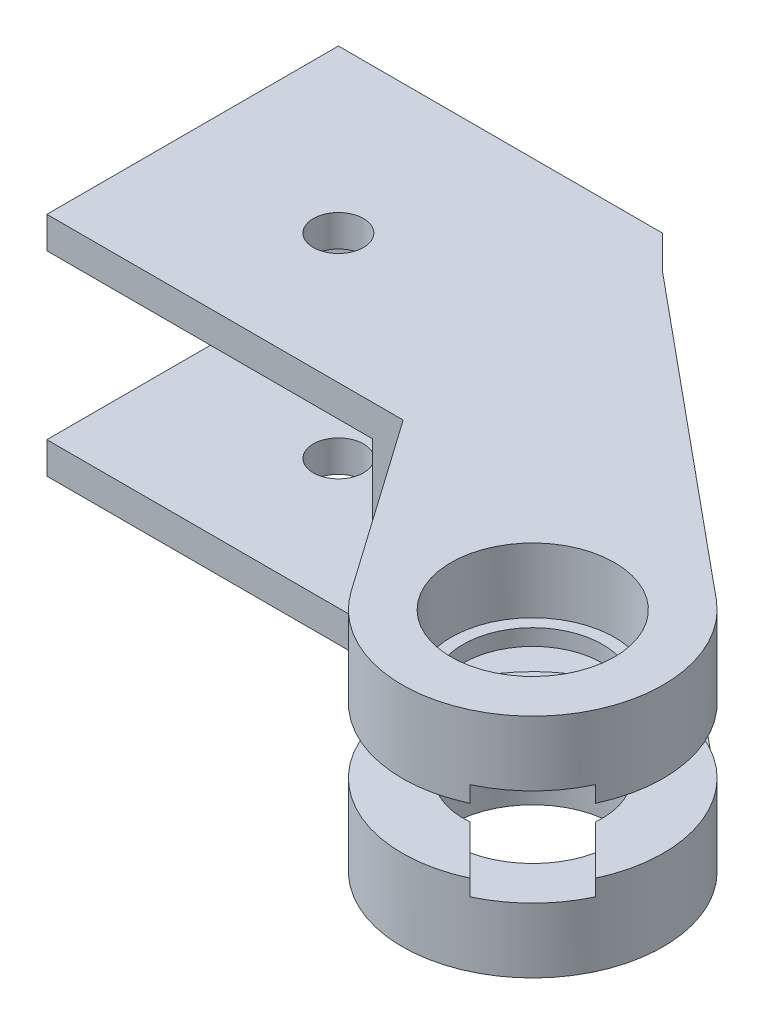
SolidWorks part; units mm, degrees
material "PET-G 50%"
ref_plane "Front Plane" through (0, 0, 0) normal (0, 0, 1) x (1, 0, 0)
ref_plane "Top Plane" through (0, 0, 0) normal (0, 1, 0) x (1, 0, 0)
ref_plane "Right Plane" through (0, 0, 0) normal (1, 0, 0) x (0, 0, -1)
sketch "Sketch1" plane through (0, 0, 0) normal (0, 1, 0) x (1, 0, 0)
  line L0 (0, 0) -> (0, 30319.3642) construction
  line L1 (-12, 8) -> (0, 8)
  line L2 (-12, 8) -> (-12, -8)
  line L3 (-12, -8) -> (0, -8)
  line L4 (0, 8) -> (0, -8)
  line L5 (0, 0) -> (30319.3642, 0) construction
  point P11 (0, -8)
  dimension "D1" = 12
  dimension "D2" = 16
extrude "Boss-Extrude1" add sketch "Sketch1" along normal mid plane 14
ref_plane "Plane1" through (0, 0, 0) normal (0, -1, 0) x (-1, 0, 0)
sketch "Sketch4" plane through (-12, 0, 0) normal (-1, 0, 0) x (0, 0, 1)
  line L0 (-8, 7) -> (-8, -7) construction
  line L1 (-8, -5.05) -> (8, -5.05)
  line L2 (-8, -5.05) -> (-8, 5.05)
  line L3 (-8, 5.05) -> (8, 5.05)
  line L4 (8, -5.05) -> (8, 5.05)
  line L5 (8, 7) -> (8, -7) construction
  line L6 (0, 0) -> (50000, 0) construction
  dimension "D1" = 10.1
extrude "Cut-Extrude1" cut sketch "Sketch4" against normal blind 10.1
sketch "Sketch5" plane through (0, -7, 0) normal (0, -1, 0) x (1, 0, 0)
  line L0 (0, 0) -> (14.1421, 14.1421) construction
  line L1 (0, 8) -> (7.552, 18.7652)
  line L2 (0, 8) -> (0, -8)
  line L3 (0, -8) -> (19.2725, 7.9387)
  line L4 (0, 0) -> (50000, 0) construction
  circle A0 centre (14.1421, 14.1421) radius 5.05
  circle A1 centre (14.1421, 14.1421) radius 8.05 construction
  arc A2 (19.2725, 7.9387) -> (7.552, 18.7652) centre (14.1421, 14.1421) ccw
  dimension "D1" = 10.1
  dimension "D2" = 3
  dimension "D3" = 20
  dimension "D4" = 45
extrude "Boss-Extrude2" add sketch "Sketch5" against normal blind 4
mirror "Mirror1" about plane through (0, 0, 0) normal (0, -1, 0) of "Boss-Extrude2"
sketch "Sketch6" plane through (0, -3, 0) normal (0, 1, 0) x (1, 0, 0)
  line L0 (14.5351, -18.4241) -> (17.5474, -21.4364)
  line L2 (0, 0) -> (19.8343, -19.8343) construction
  line L3 (21.4364, -17.5474) -> (18.4241, -14.5351)
  circle A1 centre (14.1421, -14.1421) radius 8.05 construction
  arc A2 (14.5351, -18.4241) -> (18.4241, -14.5351) centre (14.1421, -14.1421) cw
  arc A3 (7.552, -18.7652) -> (19.2725, -7.9387) centre (14.1421, -14.1421) ccw construction
  circle A4 centre (14.1421, -14.1421) radius 4.3 construction
  arc A5 (17.5474, -21.4364) -> (21.4364, -17.5474) centre (14.1421, -14.1421) cw
  dimension "D1" = 8.6
  dimension "D2" = 5.5
extrude "Boss-Extrude3" add sketch "Sketch6" along normal blind 1
mirror "Mirror2" about plane through (0, 0, 0) normal (0, -1, 0) of "Boss-Extrude3"
sketch "Sketch8" plane through (0, 3, 0) normal (0, -1, 0) x (1, 0, 0)
  line L0 (13.1076, 2.8403) -> (0, -8)
  line L1 (0, -8) -> (19.2725, 7.9387) construction
  line L2 (0, -8) -> (0, 8)
  line L3 (0, 8) -> (13.1076, 2.8403)
  dimension "D1" = 8
extrude "Boss-Extrude5" add sketch "Sketch8" along normal up to surface (6 mm away) up to face at (5.523, -3, 5.3952)
sketch "Sketch9" plane through (-12, 0, 0) normal (-1, 0, 0) x (0, 0, 1)
  line L1 (-8, 7) -> (8, 7)
  line L2 (-8, 7) -> (-8, 5.05)
  line L3 (-8, 5.05) -> (8, 5.05)
  line L4 (8, 7) -> (8, 5.05)
  line L5 (-8, -5.05) -> (8, -5.05)
  line L6 (-8, -5.05) -> (-8, -7)
  line L7 (-8, -7) -> (8, -7)
  line L8 (8, -5.05) -> (8, -7)
extrude "Boss-Extrude6" add sketch "Sketch9" along normal blind 10
sketch "Sketch10" plane through (0, 0, -8) normal (0, 0, -1) x (-1, 0, 0)
  line L1 (0, 7) -> (22, 7)
  line L2 (0, 7) -> (0, -7)
  line L3 (0, -7) -> (22, -7)
  line L4 (22, 7) -> (22, -7)
extrude "Boss-Extrude7" add sketch "Sketch10" along normal blind 2
sketch "Sketch7" plane through (0, 7, 0) normal (0, 1, 0) x (1, 0, 0)
  circle A0 centre (-12, 0) radius 1.55
  circle A4 centre (-12, 0) radius 1.55 construction
extrude "Cut-Extrude2" cut sketch "Sketch7" against normal up to surface (14 mm away) up to face at (-1.5691, -7, 3.0582)
chamfer "Chamfer1" distance 2 angle 45 1 edges at (0, 0, -10)
sketch "Sketch11" plane through (0, 0, -8) normal (0, 0, 1) x (1, 0, 0)
  line L1 (-22, 5.05) -> (-1.9, 5.05)
  line L2 (-22, 5.05) -> (-22, -5.05)
  line L3 (-22, -5.05) -> (-1.9, -5.05)
  line L4 (-1.9, 5.05) -> (-1.9, -5.05)
extrude "Cut-Extrude3" cut sketch "Sketch11" against normal blind 0.1
